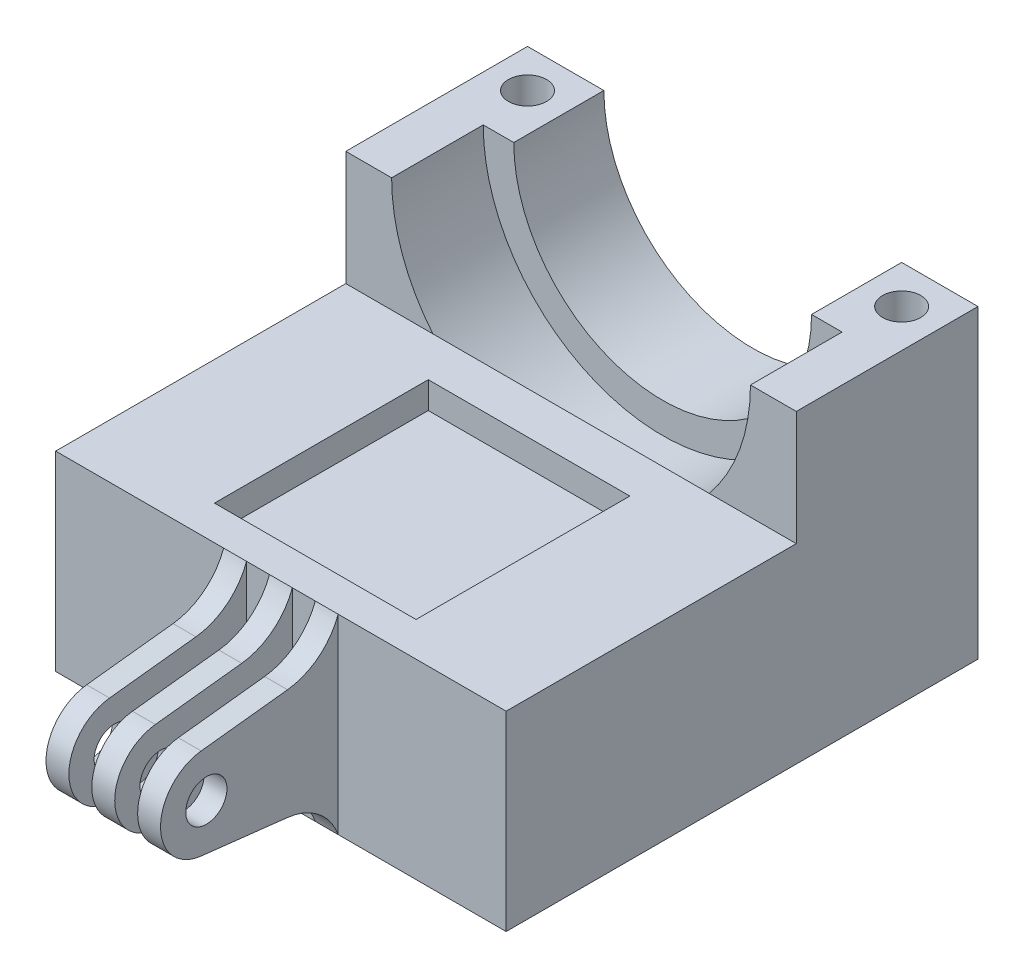
SolidWorks part; units mm, degrees
ref_plane "Front Plane" through (0, 0, 0) normal (0, 0, 1) x (1, 0, 0)
ref_plane "Top Plane" through (0, 0, 0) normal (0, 1, 0) x (1, 0, 0)
ref_plane "Right Plane" through (0, 0, 0) normal (1, 0, 0) x (0, 0, -1)
sketch "Sketch1" plane through (0, 0, 0) normal (0, 0, 1) x (1, 0, 0)
  line L0 (55, 0) -> (-55, 0) construction
  line L1 (-19.5, 0) -> (-29.5, 0)
  line L2 (-29.5, 0) -> (-29.5, -40)
  line L3 (-29.5, -40) -> (29.5, -40)
  line L4 (29.5, -40) -> (29.5, 0)
  line L5 (29.5, 0) -> (19.5, 0)
  arc A0 (-19.5, 0) -> (19.5, 0) centre (0, 0) ccw
  dimension "D1" = 19.5
  dimension "D2" = 10
  dimension "D3" = 40
extrude "Boss-Extrude1" add sketch "Sketch1" along normal blind 11.8
sketch "Sketch2" plane through (0, 0, 11.8) normal (0, 0, 1) x (1, 0, 0)
  line L0 (55, 0) -> (-55, 0) construction
  line L1 (23.4991, 0) -> (29.5, 0)
  line L2 (29.5, -40) -> (29.5, 0) construction
  line L3 (29.5, 0) -> (29.5, -40)
  line L4 (29.5, -40) -> (-29.5, -40)
  line L5 (-29.5, -40) -> (-29.5, 0)
  line L6 (-29.5, 0) -> (-29.5, -40) construction
  line L7 (-29.5, 0) -> (-23.4991, 0)
  arc A0 (-23.4991, 0) -> (23.4991, 0) centre (0, 0) ccw
  dimension "D1" = 23.4991
extrude "Boss-Extrude2" add sketch "Sketch2" along normal blind 12
sketch "Sketch3" plane through (0, 0, 23.8) normal (0, 0, 1) x (1, 0, 0)
  line L0 (-29.5, -40) -> (29.5, -40) construction
  line L1 (-29.5, -40) -> (29.5, -40)
  line L2 (-29.5, -40) -> (-29.5, -15)
  line L3 (-29.5, -15) -> (29.5, -15)
  line L4 (29.5, -40) -> (29.5, -15)
  line L5 (29.5, -40) -> (29.5, 0) construction
  dimension "D1" = 25
extrude "Boss-Extrude3" add sketch "Sketch3" along normal blind 38
sketch "Sketch4" plane through (0, -15, 0) normal (0, 1, 0) x (1, 0, 0)
  line L0 (0, -44.7868) -> (0, 44.7868) construction
  line L1 (-13.2, -57.3) -> (13.2, -57.3)
  line L2 (-13.2, -57.3) -> (-13.2, -29.3)
  line L3 (-13.2, -29.3) -> (13.2, -29.3)
  line L4 (13.2, -57.3) -> (13.2, -29.3)
  line L6 (29.5, -61.8) -> (-29.5, -61.8) construction
  point P4 (0, -29.3)
  dimension "D1" = 26.4
  dimension "D2" = 28
  dimension "D3" = 4.5
extrude "Cut-Extrude1" cut sketch "Sketch4" against normal blind 3.5
sketch "Sketch5" plane through (0, 0, 0) normal (0, 1, 0) x (1, 0, 0)
  line L0 (29.5, -23.8) -> (29.5, 0) construction
  line L1 (-29.5, -23.8) -> (-29.5, 0) construction
  line L2 (-44.2539, 0) -> (44.2539, 0) construction
  circle A0 centre (-24.5, -5) radius 2.5
  circle A1 centre (24.5, -5) radius 2.5
  dimension "D1" = 5
  dimension "D2" = 5
  dimension "D3" = 5
  dimension "D4" = 5
  dimension "D5" = 5
  dimension "D6" = 5
extrude "Cut-Extrude2" cut sketch "Sketch5" against normal through all
sketch "Sketch6" plane through (0, 0, 0) normal (1, 0, 0) x (0, 0, -1)
  line L0 (-61.8, -40) -> (-61.8, -15) construction
  line L1 (-61.8, -19.5) -> (-79.7418, -21.5384)
  line L2 (-61.8, -35.5) -> (-79.7418, -33.4616)
  line L4 (-61.8, -19.5) -> (-61.8, -35.5)
  circle A0 centre (-79.0645, -27.5) radius 2.7
  arc A1 (-79.7418, -21.5384) -> (-79.7418, -33.4616) centre (-79.0645, -27.5) ccw
  point P5 (-61.8, -27.5)
  dimension "D1" = 5.4
  dimension "D2" = 12
  dimension "D3" = 0
  dimension "D4" = 16
  dimension "D5" = 8
extrude "Boss-Extrude4" add sketch "Sketch6" along normal mid plane 3
pattern_linear "LPattern1" count 2 spacing 6 along (-1, 0, 0) count 2 spacing 6 along (1, 0, 0) of "Boss-Extrude4"
fillet "Fillet1" radius 8 6 edges at (-6, -35.5, 61.8) (0, -35.5, 61.8) (6, -35.5, 61.8) (-6, -19.5, 61.8) (0, -19.5, 61.8) (6, -19.5, 61.8)
